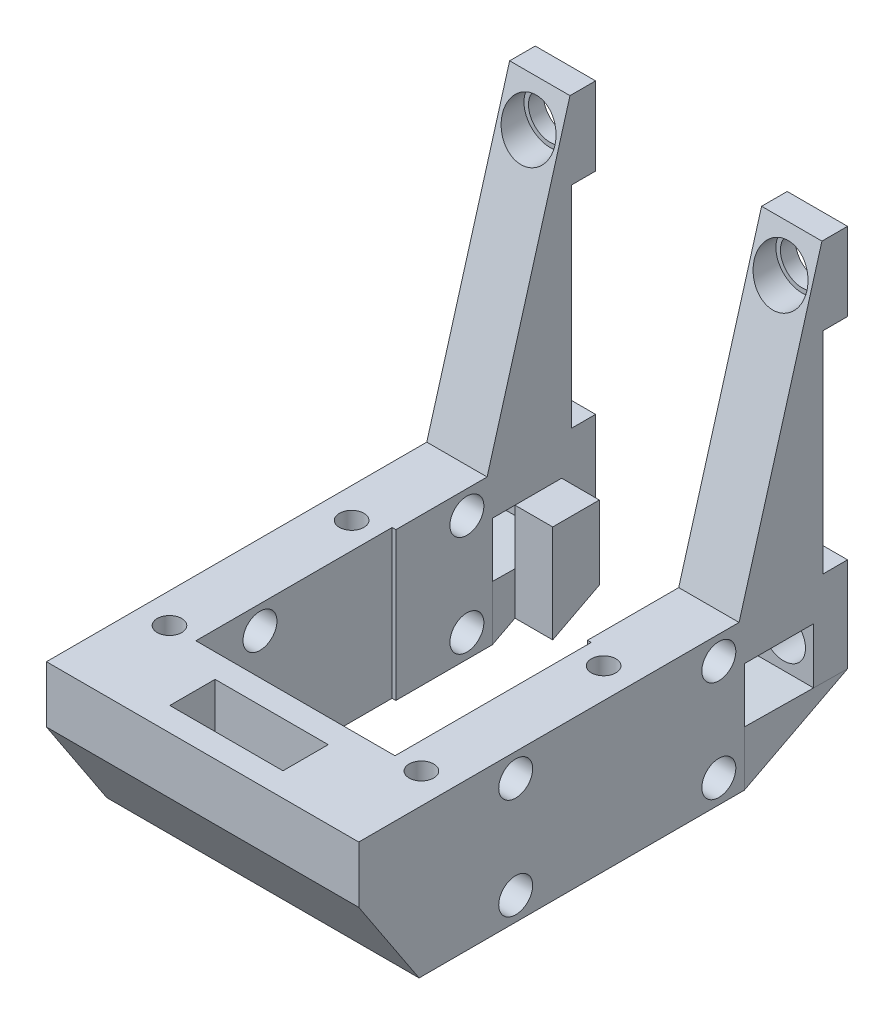
SolidWorks part; units mm, degrees
ref_plane "Front Plane" through (0, 0, 0) normal (0, 0, 1) x (1, 0, 0)
ref_plane "Top Plane" through (0, 0, 0) normal (0, 1, 0) x (1, 0, 0)
ref_plane "Right Plane" through (0, 0, 0) normal (1, 0, 0) x (0, 0, -1)
sketch "Sketch1" plane through (-474.147, -1016.1135, 5527.2949) normal (0, 0, 1) x (1, 0, 0)
  line L1 (211.6017, 683.0822) -> (219.1017, 683.0822)
  line L2 (211.6017, 683.0822) -> (211.6017, 675.5822)
  line L3 (211.6017, 675.5822) -> (219.1017, 675.5822)
  line L4 (219.1017, 683.0822) -> (219.1017, 675.5822)
  line L6 (237.0017, 683.0822) -> (237.0017, 675.5822)
  line L7 (237.0017, 675.5822) -> (229.5017, 675.5822)
  line L8 (229.5017, 683.0822) -> (229.5017, 675.5822)
  line L9 (237.0017, 683.0822) -> (229.5017, 683.0822)
  line L10 (237.0017, 718.5082) -> (229.5017, 718.5082)
  line L11 (237.0017, 711.0082) -> (237.0017, 718.5082)
  line L12 (229.5017, 711.0082) -> (229.5017, 718.5082)
  line L13 (237.0017, 711.0082) -> (229.5017, 711.0082)
  line L14 (211.6017, 718.5082) -> (219.1017, 718.5082)
  line L15 (211.6017, 711.0082) -> (211.6017, 718.5082)
  line L16 (219.1017, 711.0082) -> (219.1017, 718.5082)
  line L17 (211.6017, 711.0082) -> (219.1017, 711.0082)
  line L18 (219.1017, 675.5822) -> (229.5017, 675.5822) construction
  line L20 (237.0017, 683.0822) -> (237.0017, 711.0082) construction
  line L22 (211.6017, 683.0822) -> (211.6017, 711.0082) construction
  line L24 (219.1017, 718.5082) -> (229.5017, 718.5082) construction
  dimension "D1" = 237.1453
  dimension "D2" = 244.6453
  dimension "D3" = 255.0453
  dimension "D4" = 297.6053
  dimension "D5" = 333.0313
extrude "Boss-Extrude1" add sketch "Sketch1" along normal blind 5.5
sketch "Sketch2" plane through (0, 0, 5532.7949) normal (0, 0, 1) x (1, 0, 0)
  line L0 (-229.1453, -333.0313) -> (-229.1453, -340.5313)
  line L1 (-262.5453, -333.0313) -> (-270.5453, -333.0313)
  line L2 (-262.5453, -333.0313) -> (-262.5453, -340.5313)
  line L3 (-262.5453, -340.5313) -> (-270.5453, -340.5313)
  line L4 (-270.5453, -333.0313) -> (-270.5453, -340.5313)
  line L5 (-262.5453, -333.0313) -> (-262.5453, -340.5313) construction
  line L6 (-262.5453, -340.5313) -> (-255.0453, -340.5313) construction
  line L7 (-249.8453, -297.6053) -> (-249.8453, -340.5313) construction
  line L8 (-262.5453, -319.0683) -> (-237.1453, -319.0683) construction
  line L9 (-237.1453, -340.5313) -> (-229.1453, -340.5313)
  line L10 (-237.1453, -333.0313) -> (-237.1453, -340.5313)
  line L11 (-237.1453, -333.0313) -> (-229.1453, -333.0313)
  dimension "D1" = 7.5
  dimension "D2" = 8
  dimension "D3" = 12.7
  dimension "D4" = 21.463
extrude "Boss-Extrude2" add sketch "Sketch2" along normal blind 45 and the other way blind 5.5
sketch "Sketch3" plane through (0, 0, 5577.7949) normal (0, 0, 1) x (1, 0, 0)
  line L0 (-237.1453, -340.5313) -> (-229.1453, -340.5313) construction
  line L1 (-270.5453, -333.0313) -> (-229.1453, -333.0313)
  line L2 (-270.5453, -333.0313) -> (-270.5453, -340.5313)
  line L3 (-270.5453, -340.5313) -> (-229.1453, -340.5313)
  line L4 (-229.1453, -333.0313) -> (-229.1453, -340.5313)
  line L5 (-229.1453, -340.5313) -> (-229.1453, -333.0313) construction
extrude "Boss-Extrude3" add sketch "Sketch3" along normal blind 16
sketch "Sketch4" plane through (-262.5453, 0, 0) normal (-1, 0, 0) x (0, 0, 1)
  line L3 (5527.2949, -333.0313) -> (5527.2949, -294.744)
  line L4 (5527.2949, -294.744) -> (5532.3941, -294.744)
  line L5 (5527.2949, -297.6053) -> (5527.2949, -305.1053) construction
  line L6 (5532.3941, -294.744) -> (5543.3789, -333.0313)
  line L7 (5543.3789, -333.0313) -> (5527.2949, -333.0313)
  line L8 (5539.6853, -333.0313) -> (5577.7949, -333.0313) construction
  point P1 (0, 0)
  point P4 (0, 0)
  point P13 (5543.3789, -333.0313)
extrude "Boss-Extrude4" add sketch "Sketch4" along normal blind 8
ref_plane "Plane1" through (-249.8453, 0, 0) normal (-1, 0, 0) x (0, 0, 1)
mirror "Mirror1" about plane through (-249.8453, 0, 0) normal (-1, 0, 0) of "Boss-Extrude2", "Boss-Extrude4"
sketch "Sketch5" plane through (0, 0, 5532.7949) normal (0, 0, 1) x (1, 0, 0)
  line L0 (-258.7953, -297.6053) -> (-258.7953, -305.1053) construction
  line L1 (-255.0453, -297.6053) -> (-262.5453, -297.6053) construction
  line L2 (-262.5453, -305.1053) -> (-255.0453, -305.1053) construction
  line L3 (-255.0453, -301.3553) -> (-262.5453, -301.3553) construction
  line L4 (-255.0453, -305.1053) -> (-255.0453, -297.6053) construction
  line L5 (-262.5453, -297.6053) -> (-262.5453, -305.1053) construction
  line L6 (-255.0453, -297.6053) -> (-244.6453, -297.6053) construction
  line L7 (-249.8453, -297.6053) -> (-249.8453, -305.1053) construction
  line L8 (-255.0453, -305.1053) -> (-244.6453, -305.1053) construction
  line L9 (-255.0453, -340.5313) -> (-244.6453, -340.5313) construction
  line L10 (-255.0453, -333.0313) -> (-244.6453, -333.0313) construction
  line L11 (-249.8453, -305.1053) -> (-249.8453, -333.0313) construction
  line L12 (-255.0453, -333.0313) -> (-255.0453, -305.1053) construction
  line L13 (-249.8453, -319.0683) -> (-255.0453, -319.0683) construction
  line L14 (-244.6453, -301.3553) -> (-237.1453, -301.3553) construction
  line L15 (-240.8953, -297.6053) -> (-240.8953, -305.1053) construction
  line L16 (-244.6453, -336.7813) -> (-237.1453, -336.7813) construction
  line L17 (-240.8953, -340.5313) -> (-240.8953, -333.0313) construction
  line L18 (-258.7953, -340.5313) -> (-258.7953, -333.0313) construction
  line L19 (-255.0453, -336.7813) -> (-262.5453, -336.7813) construction
  circle A0 centre (-258.7953, -301.3553) radius 2.5
  circle A1 centre (-240.8953, -301.3553) radius 2.5
  circle A2 centre (-240.8953, -336.7813) radius 2.5
  circle A3 centre (-258.7953, -336.7813) radius 2.5
  dimension "D1" = 5
extrude "Cut-Extrude1" cut sketch "Sketch5" against normal blind 8
sketch "Sketch6" plane through (-270.5453, 0, 0) normal (-1, 0, 0) x (0, 0, 1)
  line L0 (5527.2949, -340.5313) -> (5593.7949, -340.5313) construction
  line L1 (5539.6853, -340.5313) -> (5577.7949, -340.5313)
  line L2 (5539.6853, -340.5313) -> (5539.6853, -352.6436)
  line L3 (5539.6853, -352.6436) -> (5577.7949, -352.6436)
  line L4 (5577.7949, -340.5313) -> (5577.7949, -352.6436)
extrude "Boss-Extrude6" add sketch "Sketch6" against normal blind 8
ref_plane "Plane2" through (-249.8453, 0, 0) normal (-1, 0, 0) x (0, 0, 1)
mirror "Mirror2" about plane through (-249.8453, 0, 0) normal (-1, 0, 0) of "Boss-Extrude6"
sketch "Sketch9" plane through (0, 0, 5577.7949) normal (0, 0, 1) x (1, 0, 0)
  line L0 (-262.5453, -352.6436) -> (-270.5453, -352.6436) construction
  line L1 (-270.5453, -352.6436) -> (-229.1453, -352.6436)
  line L2 (-270.5453, -352.6436) -> (-270.5453, -340.5313)
  line L3 (-270.5453, -340.5313) -> (-229.1453, -340.5313)
  line L4 (-229.1453, -352.6436) -> (-229.1453, -340.5313)
  line L5 (-270.5453, -352.6436) -> (-270.5453, -340.5313) construction
  line L6 (-270.5453, -340.5313) -> (-229.1453, -340.5313) construction
extrude "Boss-Extrude7" add sketch "Sketch9" along normal blind 8
sketch "Sketch10" plane through (-270.5453, 0, 0) normal (-1, 0, 0) x (0, 0, 1)
  line L0 (5572.9896, -336.1377) -> (5572.9896, -333.0313) construction
  line L1 (5543.3789, -333.0313) -> (5593.7949, -333.0313) construction
  line L2 (5572.9896, -352.6436) -> (5572.9896, -349.5373) construction
  line L3 (5539.6853, -352.6436) -> (5585.7949, -352.6436) construction
  circle A4 centre (5546.0612, -349.5373) radius 2.25
  circle A5 centre (5572.9896, -349.5373) radius 2.25
  circle A6 centre (5546.0612, -336.1377) radius 2.25
  circle A7 centre (5572.9896, -336.1377) radius 2.25
  dimension "D1" = 4.5
  dimension "D2" = 13.6671
  dimension "D3" = 40.5955
  dimension "D4" = 3.1064
extrude "Cut-Extrude2" cut sketch "Sketch10" against normal through all
sketch "Sketch11" plane through (-270.5453, 0, 0) normal (-1, 0, 0) x (0, 0, 1)
  line L0 (5527.2949, -340.3725) -> (5539.6853, -352.6436)
  line L1 (5527.2949, -294.744) -> (5527.2949, -340.5313) construction
  line L2 (5539.6853, -340.5313) -> (5539.6853, -352.6436) construction
  line L3 (5539.6853, -352.6436) -> (5539.6853, -340.5313)
  line L4 (5527.2949, -340.5313) -> (5539.6853, -340.5313) construction
  line L5 (5539.6853, -340.5313) -> (5527.2949, -340.3725)
  line L7 (5539.6853, -352.6436) -> (5585.7949, -352.6436) construction
  dimension "D1" = 12.2712
extrude "Boss-Extrude8" add sketch "Sketch11" against normal blind 8
sketch "Sketch12" plane through (-229.1453, 0, 0) normal (1, 0, 0) x (0, 0, -1)
  line L0 (-5539.6853, -352.6436) -> (-5527.5467, -340.5313)
  line L1 (-5539.6853, -340.5313) -> (-5539.6853, -352.6436) construction
  line L2 (-5539.6853, -340.5313) -> (-5527.2949, -340.5313) construction
  line L3 (-5527.5467, -340.5313) -> (-5539.6853, -340.5313)
  line L4 (-5539.6853, -340.5313) -> (-5539.6853, -352.6436)
  line L5 (-5527.5501, -340.8533) -> (-5527.1296, -301.2163) construction
  point P6 (-5527.5467, -340.5313)
extrude "Boss-Extrude9" add sketch "Sketch12" against normal blind 8
sketch "Sketch13" plane through (-270.5453, 0, 0) normal (-1, 0, 0) x (0, 0, 1)
  line L0 (5527.8316, -294.744) -> (5527.8316, -302.244) construction
  line L1 (5532.3941, -294.744) -> (5527.2949, -294.744) construction
  line L2 (5527.8316, -340.5313) -> (5527.8316, -333.0313) construction
  line L3 (5527.2949, -294.744) -> (5527.2949, -340.5313) construction
  line L4 (5527.2949, -333.0313) -> (5532.2204, -333.0313)
  line L5 (5527.2949, -333.0313) -> (5527.2949, -305.1053)
  line L6 (5527.2949, -305.1053) -> (5532.2204, -305.1053)
  line L7 (5532.2204, -333.0313) -> (5532.2204, -305.1053)
  point P12 (5532.2204, -333.0313)
  dimension "D1" = 7.5
  dimension "D2" = 7.5
extrude "Cut-Extrude3" cut sketch "Sketch13" against normal through all
sketch "Sketch14" plane through (-270.5453, 0, 0) normal (-1, 0, 0) x (0, 0, 1)
  line L0 (5585.7949, -352.6436) -> (5593.7949, -340.5313)
  line L1 (5585.7949, -340.5313) -> (5585.7949, -352.6436) construction
  line L2 (5585.7949, -340.5313) -> (5593.7949, -340.5313) construction
  line L3 (5593.7949, -340.5313) -> (5585.7949, -340.5313)
  line L4 (5585.7949, -340.5313) -> (5585.7949, -352.6436)
extrude "Boss-Extrude10" add sketch "Sketch14" against normal blind 41.4
sketch "Sketch16" plane through (0, -333.0313, 0) normal (0, 1, 0) x (1, 0, 0)
  line L1 (-263.0453, -5555.4748) -> (-236.6453, -5555.4748)
  line L2 (-263.0453, -5555.4748) -> (-263.0453, -5581.4885)
  line L3 (-263.0453, -5581.4885) -> (-236.6453, -5581.4885)
  line L4 (-236.6453, -5555.4748) -> (-236.6453, -5581.4885)
  line L5 (-263.0453, -5566.5853) -> (-270.5453, -5566.5853) construction
  line L6 (-270.5453, -5543.3789) -> (-270.5453, -5593.7949) construction
  line L7 (-236.6453, -5567.7425) -> (-229.1453, -5567.7425) construction
  line L8 (-229.1453, -5593.7949) -> (-229.1453, -5543.3789) construction
  line L10 (-229.1453, -5543.3789) -> (-237.1453, -5543.3789) construction
  dimension "D1" = 7.5
  dimension "D2" = 12.0959
  dimension "D3" = 23.2064
  dimension "D4" = 24.3636
  dimension "D5" = 38.1096
extrude "Cut-Extrude5" cut sketch "Sketch16" against normal through all
sketch "Sketch17" plane through (0, -297.6053, 0) normal (0, 1, 0) x (1, 0, 0)
  line L1 (-237.1453, -5527.2949) -> (-262.5453, -5527.2949)
  line L2 (-237.1453, -5527.2949) -> (-237.1453, -5532.7949)
  line L3 (-237.1453, -5532.7949) -> (-262.5453, -5532.7949)
  line L4 (-262.5453, -5527.2949) -> (-262.5453, -5532.7949)
extrude "Cut-Extrude6" cut sketch "Sketch17" against normal blind 50
sketch "Sketch18" plane through (0, -294.744, 0) normal (0, 1, 0) x (1, 0, 0)
  line L1 (-270.5453, -5527.2949) -> (-229.1453, -5527.2949)
  line L2 (-270.5453, -5527.2949) -> (-270.5453, -5528.9982)
  line L3 (-270.5453, -5528.9982) -> (-229.1453, -5528.9982)
  line L4 (-229.1453, -5527.2949) -> (-229.1453, -5528.9982)
  line L5 (-229.1453, -5532.3941) -> (-229.1453, -5527.2949) construction
  point P5 (-229.1453, -5528.9982)
  point P7 (0, 0)
extrude "Cut-Extrude7" cut sketch "Sketch18" against normal blind 50
sketch "Sketch19" plane through (0, 0, 5528.9982) normal (0, 0, -1) x (-1, 0, 0)
  line L0 (233.1453, -294.744) -> (233.1453, -305.1053) construction
  line L1 (237.1453, -294.744) -> (229.1453, -294.744) construction
  line L2 (237.1453, -305.1053) -> (229.1453, -305.1053) construction
  line L3 (229.1453, -299.9246) -> (237.1453, -299.9246) construction
  line L4 (229.1453, -305.1053) -> (229.1453, -294.744) construction
  line L5 (237.1453, -305.1053) -> (237.1453, -294.744) construction
  circle A0 centre (233.1453, -299.9246) radius 2.9
  dimension "D1" = 5.8
extrude "Cut-Extrude8" cut sketch "Sketch19" against normal blind 50
ref_plane "Plane3" through (0, 0, 5538.9982) normal (0, 0, -1) x (-1, 0, 0)
sketch "Sketch20" plane through (0, 0, 5538.9982) normal (0, 0, -1) x (-1, 0, 0)
  circle A1 centre (233.1453, -299.9246) radius 3.5
  dimension "D1" = 7
extrude "Cut-Extrude9" cut sketch "Sketch20" along normal blind 8
ref_plane "Plane4" through (-249.8453, 0, 0) normal (-1, 0, 0) x (0, 0, 1)
mirror "Mirror3" about plane through (-249.8453, 0, 0) normal (-1, 0, 0) of "Cut-Extrude9", "Cut-Extrude8"
ref_plane "Plane5" through (0, -319.0683, 0) normal (0, 1, 0) x (1, 0, 0)
sketch "Sketch21" plane through (-270.5453, 0, 0) normal (-1, 0, 0) x (0, 0, 1)
  line L0 (5528.9982, -342.0594) -> (5528.9982, -333.0313) construction
  line L1 (5528.9982, -338.1154) -> (5539.6853, -338.1154)
  line L2 (5528.9982, -338.1154) -> (5528.9982, -352.6436)
  line L3 (5528.9982, -352.6436) -> (5539.6853, -352.6436)
  line L4 (5539.6853, -338.1154) -> (5539.6853, -352.6436)
extrude "Cut-Extrude10" cut sketch "Sketch21" against normal blind 55
sketch "Sketch22" plane through (0, -338.1154, 0) normal (0, -1, 0) x (1, 0, 0)
  line L0 (-262.5453, 5528.9982) -> (-262.5453, 5539.6853) construction
  line L1 (-270.5453, 5528.9982) -> (-262.5453, 5528.9982)
  line L2 (-270.5453, 5528.9982) -> (-270.5453, 5533.4982)
  line L3 (-270.5453, 5533.4982) -> (-262.5453, 5533.4982)
  line L4 (-262.5453, 5528.9982) -> (-262.5453, 5533.4982)
  dimension "D1" = 4.5
extrude "Boss-Extrude11" add sketch "Sketch22" along normal blind 7.4279
mirror "Mirror5" about plane through (-249.8453, 0, 0) normal (-1, 0, 0) of "Boss-Extrude11"
sketch "Sketch23" plane through (0, 0, 5528.9982) normal (0, 0, -1) x (-1, 0, 0)
  circle A0 centre (233.1189, -341.4699) radius 2.9
  dimension "D1" = 5.8
extrude "Cut-Extrude11" cut sketch "Sketch23" against normal blind 5
ref_plane "Plane6" through (-270.5453, -338.1154, 5539.6853) normal (0, 1, 0) x (1, 0, 0)
sketch "Sketch25" plane through (-262.5453, 0, 0) normal (1, 0, 0) x (0, 0, -1)
  line L0 (-5539.6853, -338.1154) -> (-5533.4982, -338.1154) construction
  line L1 (-5539.6853, -352.6436) -> (-5533.4982, -352.6436)
  line L2 (-5539.6853, -352.6436) -> (-5539.6853, -338.1154)
  line L3 (-5539.6853, -338.1154) -> (-5533.4982, -338.1154)
  line L4 (-5533.4982, -352.6436) -> (-5533.4982, -338.1154)
  point P6 (-5539.1835, -338.1154)
  point P9 (-5539.6853, -338.1154)
extrude "Boss-Extrude12" add sketch "Sketch25" along normal blind 5 separate body
sketch "Sketch26" plane through (-270.5453, 0, 0) normal (-1, 0, 0) x (0, 0, 1)
  line L0 (5539.6853, -352.6436) -> (5585.7949, -352.6436) construction
  line L1 (5539.6853, -338.1154) -> (5542.6853, -338.1154)
  line L2 (5539.6853, -338.1154) -> (5539.6853, -352.6436)
  line L3 (5539.6853, -352.6436) -> (5542.6853, -352.6436)
  line L4 (5542.6853, -338.1154) -> (5542.6853, -352.6436)
  point P5 (5542.6853, -352.6436)
  dimension "D1" = 3
extrude "Cut-Extrude12" cut sketch "Sketch26" against normal through all
sketch "Sketch27" plane through (-270.5453, 0, 0) normal (-1, 0, 0) x (0, 0, 1)
  line L0 (5542.6853, -352.6436) -> (5528.9982, -345.5433)
  line L1 (5528.9982, -345.5433) -> (5542.6853, -345.3795)
  line L2 (5542.6853, -352.6436) -> (5542.6853, -338.1154) construction
  line L3 (5542.6853, -345.3795) -> (5542.6853, -352.6436)
extrude "Boss-Extrude15" add sketch "Sketch27" against normal up to surface (8 mm away) separate body up to face at (-262.5453, -345.3795, 5536.5917)
mirror "Mirror6" about plane through (-249.8453, 0, 0) normal (-1, 0, 0) of "Cut-Extrude11"
sketch "Sketch28" plane through (-262.5453, 0, 0) normal (-1, 0, 0) x (0, 0, 1)
  line L0 (5533.4982, -347.8777) -> (5539.6853, -351.0873)
  line L1 (5542.6853, -352.6436) -> (5528.9982, -345.5433) construction
  line L2 (5533.4982, -352.6436) -> (5533.4982, -338.1154) construction
  line L3 (5539.6853, -338.1154) -> (5539.6853, -352.6436) construction
  line L4 (5539.6853, -351.0873) -> (5539.6853, -359.5636)
  line L5 (5539.6853, -377.1583) -> (5539.6853, -333.0313) construction
  line L6 (5539.6853, -359.5636) -> (5533.2622, -359.5636)
  line L7 (5533.2622, -359.5636) -> (5533.4982, -347.8777)
extrude "Cut-Extrude13" cut sketch "Sketch28" against normal through all
mirror "Mirror11" about plane through (-249.8453, 0, 0) normal (-1, 0, 0) of bodies 170 168
sketch "Sketch29" plane through (0, -333.0313, 0) normal (0, 1, 0) x (1, 0, 0)
  line L0 (-249.8453, -5593.7949) -> (-249.8453, -5581.4885) construction
  line L1 (-229.1453, -5593.7949) -> (-270.5453, -5593.7949) construction
  line L2 (-263.0453, -5581.4885) -> (-236.6453, -5581.4885) construction
  line L4 (-242.3453, -5584.6417) -> (-257.3453, -5584.6417)
  line L5 (-242.3453, -5584.6417) -> (-242.3453, -5590.6417)
  line L6 (-242.3453, -5590.6417) -> (-257.3453, -5590.6417)
  line L7 (-257.3453, -5584.6417) -> (-257.3453, -5590.6417)
  line L8 (-242.3453, -5584.6417) -> (-257.3453, -5590.6417) construction
  line L9 (-242.3453, -5590.6417) -> (-257.3453, -5584.6417) construction
  point P6 (-249.8453, -5587.6417)
  dimension "D1" = 15
  dimension "D2" = 6
extrude "Cut-Extrude14" cut sketch "Sketch29" against normal blind 10
sketch "Sketch30" plane through (0, -333.0313, 0) normal (0, 1, 0) x (1, 0, 0)
  line L0 (-270.5453, -5557.3356) -> (-266.5453, -5557.3356) construction
  line L1 (-270.5453, -5543.3789) -> (-270.5453, -5593.7949) construction
  line L2 (-266.5453, -5543.3789) -> (-266.5453, -5565.5846) construction
  line L3 (-270.5453, -5543.3789) -> (-262.5453, -5543.3789) construction
  circle A0 centre (-266.5453, -5557.3356) radius 1.625
  dimension "D1" = 3.25
extrude "Cut-Extrude15" cut sketch "Sketch30" against normal blind 10
sketch "Sketch31" plane through (0, -333.0313, 0) normal (0, 1, 0) x (1, 0, 0)
  line L0 (-229.1453, -5581.4885) -> (-234.0224, -5581.4885) construction
  line L1 (-229.1453, -5593.7949) -> (-229.1453, -5543.3789) construction
  line L2 (-263.0453, -5581.4885) -> (-236.6453, -5581.4885) construction
  line L3 (-233.1453, -5543.3789) -> (-233.1453, -5581.4885) construction
  line L4 (-229.1453, -5543.3789) -> (-237.1453, -5543.3789) construction
  circle A0 centre (-233.1453, -5581.4885) radius 1.625
  dimension "D1" = 3.25
extrude "Cut-Extrude16" cut sketch "Sketch31" against normal blind 10
ref_plane "Plane7" through (-249.8453, 0, 0) normal (-1, 0, 0) x (0, 0, 1)
mirror "Mirror12" about plane through (-249.8453, 0, 0) normal (-1, 0, 0) of "Cut-Extrude16", "Cut-Extrude15"
